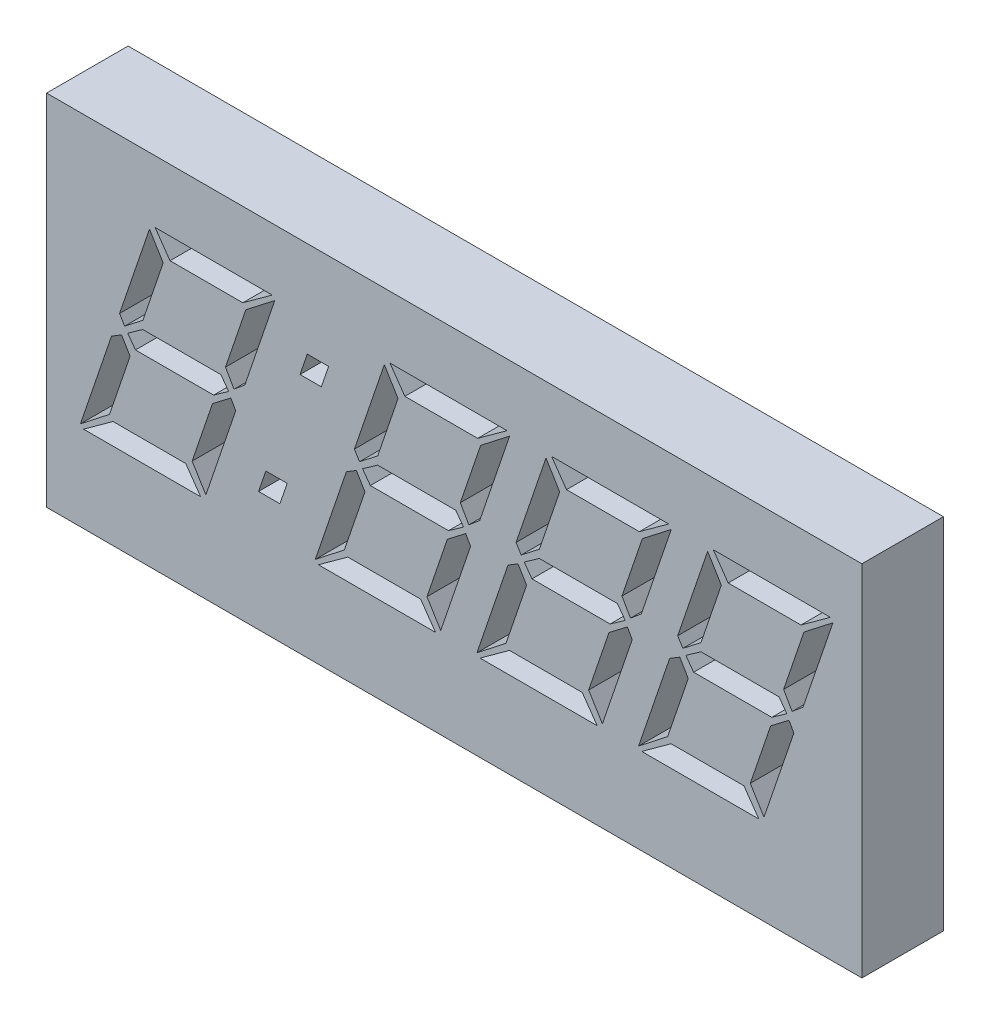
SolidWorks part; units mm, degrees
ref_plane "Спереди" through (0, 0, 0) normal (0, 0, 1) x (1, 0, 0)
ref_plane "Сверху" through (0, 0, 0) normal (0, 1, 0) x (1, 0, 0)
ref_plane "Справа" through (0, 0, 0) normal (1, 0, 0) x (0, 0, -1)
sketch "Эскиз1" plane through (0, 0, 0) normal (0, 0, 1) x (1, 0, 0)
  line L9 (65.1785, -93.2379) -> (565.1785, -93.2379)
  line L10 (65.1785, -93.2379) -> (65.1785, -313.2379)
  line L11 (65.1785, -313.2379) -> (565.1785, -313.2379)
  line L12 (565.1785, -93.2379) -> (565.1785, -313.2379)
  text T0 "<i>8:888</i>" font "DS-Digital" height 130
  point P5 (219.302, -198.1797)
  dimension "D1" = 500
  dimension "D2" = 220
extrude "Бобышка-Вытянуть1" add sketch "Эскиз1" along normal blind 50
sketch "Эскиз2" plane through (0, 0, 50) normal (0, 0, 1) x (1, 0, 0)
  line L0 (225.057, -151.9154) -> (238.1505, -151.9154)
  line L1 (238.1505, -151.9154) -> (233.6789, -165.009)
  line L2 (233.6789, -165.009) -> (220.5853, -165.009)
  line L3 (220.5853, -165.009) -> (225.057, -151.9154)
  line L4 (199.6439, -226.7311) -> (212.7374, -226.7311)
  line L5 (212.7374, -226.7311) -> (208.2658, -239.8246)
  line L6 (208.2658, -239.8246) -> (195.1722, -239.8246)
  line L7 (195.1722, -239.8246) -> (199.6439, -226.7311)
  line L8 (303.7058, -260.4046) -> (231.896, -260.4046) construction
  dimension "D1" = 20.58
  dimension "D2" = 13.0935
  dimension "D3" = 13.836
  dimension "D4" = 0
extrude "Вырез-Вытянуть1" cut sketch "Эскиз2" against normal blind 65
sketch "Эскиз3" plane through (0, 0, 50) normal (0, 0, 1) x (1, 0, 0)
  line L1 (183.9606, -243.9126) -> (208.9541, -243.9126)
  line L2 (183.9606, -243.9126) -> (183.9606, -268.6669)
  line L3 (183.9606, -268.6669) -> (208.9541, -268.6669)
  line L4 (208.9541, -243.9126) -> (208.9541, -268.6669)
extrude "Бобышка-Вытянуть2" add sketch "Эскиз3" against normal blind 50
